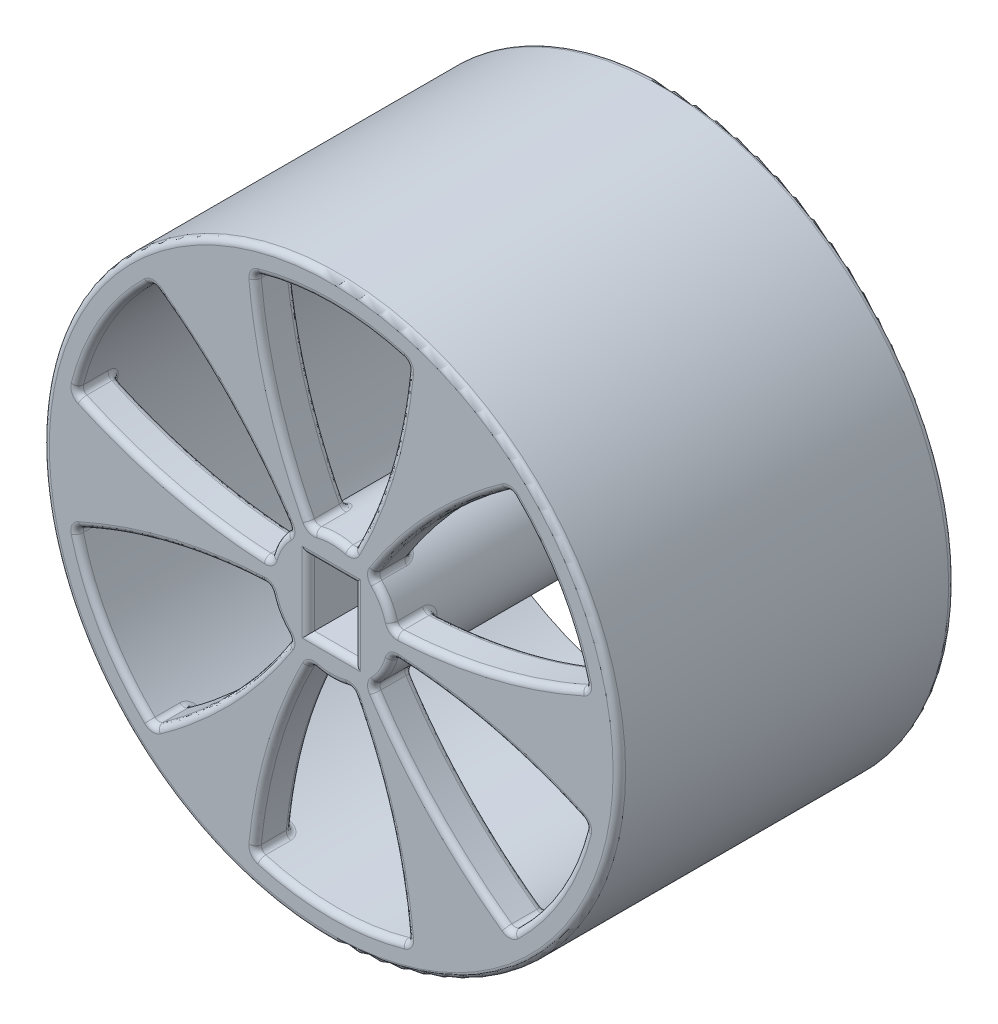
SolidWorks part; units mm, degrees
ref_plane "Front Plane" through (0, 0, 0) normal (0, 0, 1) x (1, 0, 0)
ref_plane "Top Plane" through (0, 0, 0) normal (0, 1, 0) x (1, 0, 0)
ref_plane "Right Plane" through (0, 0, 0) normal (1, 0, 0) x (0, 0, -1)
sketch "Sketch1" plane through (0, 0, 0) normal (0, 0, 1) x (1, 0, 0)
  line L0 (0, 0) -> (23.1, 0)
  line L1 (0, 0) -> (-21, 0)
  line L2 (0, 0) -> (0, -1.9)
  circle A1 centre (0, 0) radius 23.1
  circle A2 centre (0, 0) radius 21
  dimension "D1" = 23.1
  dimension "D2" = 21
extrude "Boss-Extrude1" add sketch "Sketch1" along normal blind 26.9 contours A2 | A1
sketch "Sketch2" plane through (0, 0, 26.9) normal (0, 0, 1) x (1, 0, 0)
  line L0 (0, 0) -> (1.835, 0) construction
  line L1 (0, 0) -> (0, -2.7015) construction
  line L2 (0, 0) -> (-2.75, 4.1759) construction
  line L3 (1.835, -2.7015) -> (-1.835, -2.7015)
  line L4 (1.835, -2.7015) -> (1.835, 2.7015)
  line L5 (1.835, 2.7015) -> (-1.835, 2.7015)
  line L6 (-1.835, -2.7015) -> (-1.835, 2.7015)
  circle A0 centre (0, 0) radius 5
sketch "Sketch3" plane through (0, 0, 26.9) normal (0, 0, 1) x (1, 0, 0)
  line L0 (1.835, 0) -> (5, 0) construction
  line L1 (1.835, -2.7015) -> (1.835, 2.7015) construction
  line L2 (3.4175, -0.9) -> (3.4175, 0.9) construction
  line L3 (3.4175, 0.9) -> (20.9807, 0.9) construction
  line L4 (3.4175, -0.9) -> (20.9807, -0.9) construction
  line L5 (12.1991, 0.9) -> (12.1991, -49999.1) construction
  line L6 (20.4624, -4.7211) -> (20.4624, 4.7211) construction
  line L7 (12.2093, -1.8977) -> (12.1889, 1.8977) construction
  line L8 (0, 0) -> (0, 50000) construction
  line L9 (3.4175, -0.9) -> (3.4175, 0.9)
  line L10 (0.9293, -3.4096) -> (2.4882, -2.5096)
  line L11 (-2.4882, -2.5096) -> (-0.9293, -3.4096)
  line L12 (-3.4175, 0.9) -> (-3.4175, -0.9)
  line L13 (-0.9293, 3.4096) -> (-2.4882, 2.5096)
  line L14 (2.4882, 2.5096) -> (0.9293, 3.4096)
  circle A0 centre (0, 0) radius 5 construction
  circle A1 centre (0, 0) radius 21 construction
  arc A2 (20.4624, 4.7211) -> (20.4624, -4.7211) centre (0, 0) cw
  arc A3 (14.3198, -15.3604) -> (6.1426, -20.0815) centre (0, 0) cw
  arc A4 (-6.1426, -20.0815) -> (-14.3198, -15.3604) centre (0, 0) cw
  arc A5 (-20.4624, -4.7211) -> (-20.4624, 4.7211) centre (0, 0) cw
  arc A6 (-14.3198, 15.3604) -> (-6.1426, 20.0815) centre (0, 0) cw
  arc A7 (6.1426, 20.0815) -> (14.3198, 15.3604) centre (0, 0) cw
  spline S0 degree 2 poles (3.4175, 0.9) (12.3547, 0.9662) (20.4624, 4.7211) knots 0 0 0 1 1 1
  spline S1 degree 2 poles (3.4175, -0.9) (12.3569, -0.9574) (20.4624, -4.7211) knots 0 0 0 1 1 1
  spline S2 degree 2 poles (2.4882, -2.5096) (7.0091, -10.2215) (14.3198, -15.3604) knots 0 0 0 1 1 1
  spline S3 degree 2 poles (0.9293, -3.4096) (5.3694, -11.1746) (6.1426, -20.0815) knots 0 0 0 1 1 1
  spline S4 degree 2 poles (-0.9293, -3.4096) (-5.3476, -11.1808) (-6.1426, -20.0815) knots 0 0 0 1 1 1
  spline S5 degree 2 poles (-2.4882, -2.5096) (-6.9928, -10.2373) (-14.3198, -15.3604) knots 0 0 0 1 1 1
  spline S6 degree 2 poles (-3.4175, -0.9) (-12.3567, -0.9593) (-20.4624, -4.7211) knots 0 0 0 1 1 1
  spline S7 degree 2 poles (-3.4175, 0.9) (-12.3622, 0.9373) (-20.4624, 4.7211) knots 0 0 0 1 1 1
  spline S8 degree 2 poles (-2.4882, 2.5096) (-7.0091, 10.2215) (-14.3198, 15.3604) knots 0 0 0 1 1 1
  spline S9 degree 2 poles (-0.9293, 3.4096) (-5.3694, 11.1746) (-6.1426, 20.0815) knots 0 0 0 1 1 1
  spline S10 degree 2 poles (0.9293, 3.4096) (5.3476, 11.1808) (6.1426, 20.0815) knots 0 0 0 1 1 1
  spline S11 degree 2 poles (2.4882, 2.5096) (6.9928, 10.2373) (14.3198, 15.3604) knots 0 0 0 1 1 1
  point P10 (3.4175, 0)
  point P16 (12.1991, 0.9)
  point P17 (12.1991, -0.9)
  point P24 (20.4624, 0)
  point P25 (12.1991, 0)
  point P67 (0, 0)
  circle M3 centre (0, 0) radius 21
  dimension "D1" = 1
  dimension "D2" = 6
extrude "Boss-Extrude2" add sketch "Sketch2" against normal blind 34 separate body contours L4 L5 L6 L3 | A0
extrude "Boss-Extrude5" add sketch "Sketch3" against normal blind 3 contours L11 S5 S4 M3 | L12 S7 S6 M3 | L13 S9 S8 M3 | L14 S11 S10 M3 | L9 S1 S0 M3 | S2 A3 S3 L10 region at (14.6991, 0.0014, 26.9) region at (7.3492, 12.7363, 26.9) region at (-7.3492, -12.7363, 26.9) region at (-7.3554, 12.7328, 26.9) region at (-14.7046, -0.0035, 26.9)
fillet "Fillet4" radius 0.5 48 edges at (14.3198, -15.3604, 25.4) (6.1426, -20.0815, 25.4) (3.2664, -3.7856, 25.4) (1.6485, -4.7204, 25.4) (-6.1426, -20.0815, 25.4) (-14.3198, -15.3604, 25.4) (-1.6452, -4.7216, 25.4) (-3.2638, -3.7878, 25.4) (-4.9123, 0.9326, 25.4) (-20.4624, 4.7211, 25.4) (-20.4624, -4.7211, 25.4) (-4.9116, -0.936, 25.4) (-1.6485, 4.7204, 25.4) (-6.1426, 20.0815, 25.4) (-14.3198, 15.3604, 25.4) (-3.2664, 3.7856, 25.4) (3.2638, 3.7878, 25.4) (14.3198, 15.3604, 25.4) (6.1426, 20.0815, 25.4) (1.6452, 4.7216, 25.4) (4.9117, -0.9357, 25.4) (20.4624, -4.7211, 25.4) (20.4624, 4.7211, 25.4) (4.9114, 0.9371, 25.4) (10.5, -18.1865, 23.9) (2.5015, -4.3293, 23.9) (-10.5, -18.1865, 23.9) (-2.4985, -4.331, 23.9) (-21, 0, 23.9) (-5, -0.0017, 23.9) (-10.5, 18.1865, 23.9) (-2.5015, 4.3293, 23.9) (10.5, 18.1865, 23.9) (2.4985, 4.331, 23.9) (21, 0, 23.9) (5, 0.0007, 23.9)
fillet "Fillet5" radius 0.5 1 edges at (5, 0, -7.1)
fillet "Fillet6" radius 0.5 53 edges at (23.1, 0, 26.9) (-20.3301, -4.7868, 26.9) (-18.1863, -10.5005, 26.9) (-14.3104, -15.2137, 26.9) (-3.4116, -3.8175, 26.9) (-4.3291, -2.5017, 26.9) (-5.0112, -1.0496, 26.9) (-14.3106, 15.213, 26.9) (-18.1868, 10.4995, 26.9) (-20.3307, 4.7864, 26.9) (-5.0118, 1.0458, 26.9) (-4.3311, 2.4983, 26.9) (-3.4146, 3.8151, 26.9) (6.0196, 19.9998, 26.9) (-0.0005, 21, 26.9) (-6.0202, 20, 26.9) (-1.6002, 4.8633, 26.9) (-0.002, 5, 26.9) (1.5966, 4.8647, 26.9) (20.33, 4.787, 26.9) (18.1862, 10.5006, 26.9) (14.3104, 15.2137, 26.9) (3.4116, 3.8175, 26.9) (4.3288, 2.5023, 26.9) (5.0111, 1.0508, 26.9) (-6.0196, -19.9998, 26.9) (0.0005, -21, 26.9) (6.0202, -20, 26.9) (1.6002, -4.8633, 26.9) (0.002, -5, 26.9) (-1.5966, -4.8647, 26.9) (0, 2.7015, 26.9) (-1.835, 0, 26.9) (0, -2.7015, 26.9) (1.835, 0, 26.9) (14.3106, -15.213, 26.9) (18.1866, -10.5, 26.9) (20.3302, -4.7868, 26.9) (5.0113, -1.0493, 26.9) (4.3302, -2.4999, 26.9) (3.4146, -3.8151, 26.9)
fillet "Fillet7" radius 0.5 1 edges at (23.1, 0, 0)
fillet "Fillet8" radius 0.5 4 edges at (-1.835, 0, -7.1) (0, 2.7015, -7.1) (1.835, 0, -7.1) (0, -2.7015, -7.1)
